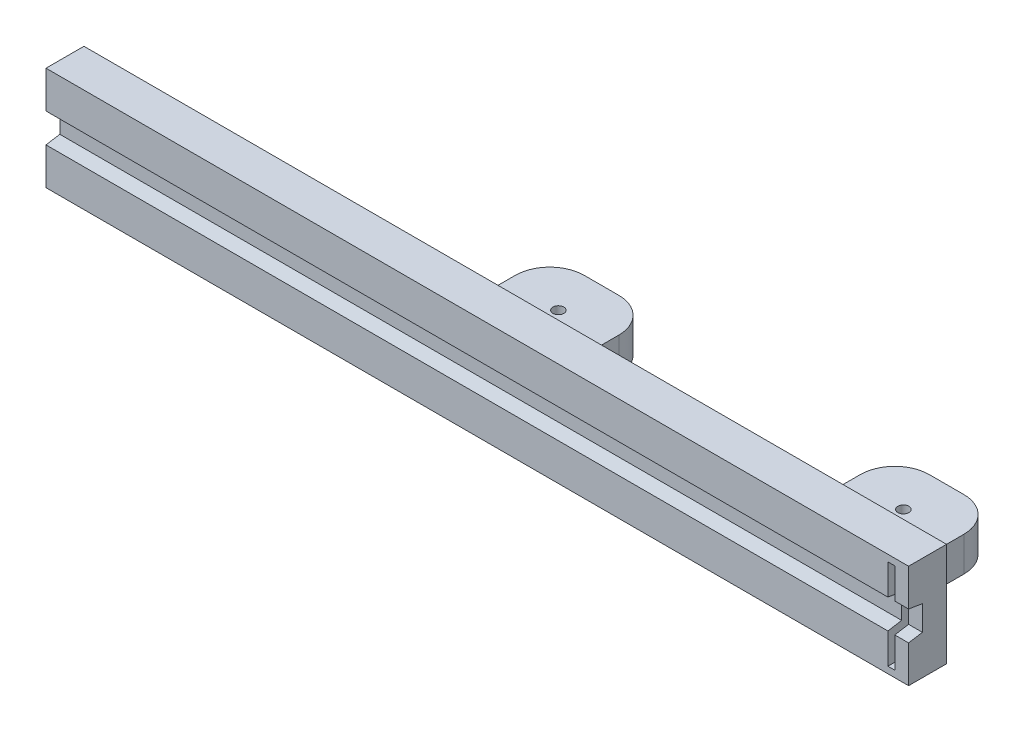
SolidWorks part; units mm, degrees
ref_plane "前基準面" through (0, 0, 0) normal (0, 0, 1) x (1, 0, 0)
ref_plane "上基準面" through (0, 0, 0) normal (0, 1, 0) x (1, 0, 0)
ref_plane "右基準面" through (0, 0, 0) normal (1, 0, 0) x (0, 0, -1)
sketch "草圖1" plane through (0, 0, 0) normal (0, 0, 1) x (1, 0, 0)
  line L0 (0, 0) -> (250, 0)
  line L1 (250, 0) -> (250, 30)
  line L2 (250, 30) -> (0, 30)
  line L3 (0, 30) -> (0, 0)
  dimension "D1" = 30
  dimension "D2" = 250
extrude "填料-伸長1" add sketch "草圖1" along normal blind 11
sketch "草圖4" plane through (0, 0, 0) normal (0, 0, -1) x (-1, 0, 0)
  line L0 (-250, 15) -> (0, 15)
  line L1 (-250, 0) -> (-250, 30) construction
  line L2 (0, 30) -> (0, 0) construction
  line L3 (-125, 30) -> (-125, 0)
  line L4 (-250, 30) -> (0, 30) construction
  line L5 (0, 0) -> (-250, 0) construction
  line L6 (-140, 15) -> (-125, 15)
  line L7 (-125, 15) -> (-110, 15)
  line L8 (-140, 15) -> (-140, 20)
  line L9 (-140, 20) -> (-110, 20)
  line L10 (-110, 20) -> (-110, 15)
  line L11 (-140, 15) -> (-140, 10)
  line L12 (-140, 10) -> (-125, 10)
  line L13 (-125, 10) -> (-110, 10)
  line L14 (-110, 10) -> (-110, 15)
  line L16 (-164.6389, 10) -> (-194.6389, 10)
  line L17 (-164.6389, 10) -> (-164.6389, 20)
  line L18 (-164.6389, 20) -> (-194.6389, 20)
  line L19 (-194.6389, 10) -> (-194.6389, 20)
  line L20 (-164.6389, 10) -> (-194.6389, 20) construction
  line L21 (-164.6389, 20) -> (-194.6389, 10) construction
  point P17 (-179.6389, 15)
  dimension "D1" = 15
  dimension "D2" = 15
  dimension "D3" = 5
  dimension "D4" = 5
  dimension "D5" = 10
  dimension "D6" = 30
extrude "填料-伸長2" add sketch "草圖4" along normal blind 25 contours L11 L12 L3 L0 | L9 L8 L0 L3 | L10 L9 L3 L0 | L13 L14 L0 L3 region at (132.5, 17.5, 0) region at (132.5, 12.5, 0) region at (117.5, 17.5, 0) region at (117.5, 12.5, 0)
sketch "草圖5" plane through (250, 0, 0) normal (1, 0, 0) x (0, 0, -1)
  line L0 (-11, 30) -> (-11, 19.25)
  line L1 (-11, 0) -> (-11, 30) construction
  line L2 (-7, 15) -> (-7, 11.402)
  line L3 (-7, 15) -> (-7, 18.6)
  line L4 (-7, 18.6) -> (-11, 19.25)
  line L5 (-11, 10.75) -> (-11, 0)
  line L6 (-11, 15) -> (0, 15)
  line L7 (0, 30) -> (0, 0) construction
  line L8 (-7, 11.402) -> (-11, 10.75)
  line L9 (-11, 10.75) -> (-11, 19.25)
  line M6 (-11, 30) -> (-11, 0)
  dimension "D1" = 8.5
  dimension "D2" = 10.75
  dimension "D3" = 10.75
  dimension "D4" = 3.6
  dimension "D5" = 3.598
  dimension "D6" = 4
extrude "除料-伸長2" cut sketch "草圖5" against normal through all contours L6 L3 L4 M6 | L8 L2 L6 M6 region at (250, 16.967, 9.0552) region at (250, 13.0335, 9.0554)
sketch "草圖6" plane through (0, 10, 0) normal (0, -1, 0) x (1, 0, 0)
  line L0 (125, 0) -> (125, -25)
  line L1 (250, 0) -> (0, 0) construction
  line L2 (140, -25) -> (110, -25) construction
  line L3 (110, -12.5) -> (140, -12.5)
  line L4 (110, -25) -> (110, 0) construction
  line L5 (140, -25) -> (140, 0) construction
  circle A0 centre (125, -12.5) radius 1.6
  dimension "D1" = 3.2
extrude "除料-伸長3" cut sketch "草圖6" against normal through all contours L3 A0 L0 | L0 A0 L3 | L3 A0 L0 | L0 A0 L3 region at (125.6791, 10, -11.8209) region at (124.3209, 10, -11.8209) region at (125.6791, 10, -13.1791) region at (124.3209, 10, -13.1791)
sketch "草圖7" plane through (0, 10, 0) normal (0, -1, 0) x (1, 0, 0)
  line L0 (125, -14.1) -> (125, -25)
  line L1 (140, -25) -> (110, -25) construction
  circle A0 centre (125, -12.5) radius 1.6 construction
sketch "草圖9" plane through (0, 0, 0) normal (0, 0, -1) x (-1, 0, 0)
  line L1 (-194.6389, 20) -> (-164.6389, 20)
  line L2 (-194.6389, 20) -> (-194.6389, 10)
  line L3 (-194.6389, 10) -> (-164.6389, 10)
  line L4 (-164.6389, 20) -> (-164.6389, 10)
  line L5 (-194.6389, 20) -> (-164.6389, 10) construction
  line L6 (-194.6389, 10) -> (-164.6389, 20) construction
  point P0 (-179.6389, 15)
sketch "草圖11" plane through (0, 0, 0) normal (0, 0, -1) x (-1, 0, 0)
  line L0 (-125, 15) -> (-225, 15)
  line L1 (-250, 15) -> (0, 15) construction
  line L3 (-240, 10) -> (-210, 10)
  line L4 (-240, 10) -> (-240, 20)
  line L5 (-240, 20) -> (-210, 20)
  line L6 (-210, 10) -> (-210, 20)
  line L7 (-240, 10) -> (-210, 20) construction
  line L8 (-240, 20) -> (-210, 10) construction
  dimension "D1" = 100
  dimension "D2" = 10
  dimension "D3" = 30
extrude "填料-伸長4" add sketch "草圖11" along normal blind 25 contours L3 L6 L5 L4 region at (239.6838, 15, 0)
sketch "草圖12" plane through (0, 20, 0) normal (0, 1, 0) x (1, 0, 0)
  line L0 (240, 12.5) -> (210, 12.5)
  line L1 (240, 25) -> (240, 0) construction
  line L2 (210, 25) -> (210, 0) construction
  circle A0 centre (225, 12.5) radius 1.6
  dimension "D1" = 3.2
extrude "除料-伸長5" cut sketch "草圖12" against normal through all contours A0
fillet "圓角1" radius 10 4 edges at (110, 15, -25) (140, 15, -25) (210, 15, -25) (240, 15, -25)
sketch "草圖13" plane through (0, 0, 11) normal (0, 0, 1) x (1, 0, 0)
  line L1 (244, 28.1) -> (246, 28.1)
  line L2 (244, 28.1) -> (244, 1.9)
  line L3 (244, 1.9) -> (246, 1.9)
  line L4 (246, 28.1) -> (246, 1.9)
  line L5 (250, 15) -> (0, 15) construction
  line L6 (250, 0) -> (250, 30) construction
  dimension "D1" = 2
  dimension "D2" = 26.2
  dimension "D3" = 13.1
  dimension "D4" = 4
extrude "除料-伸長6" cut sketch "草圖13" against normal blind 7
